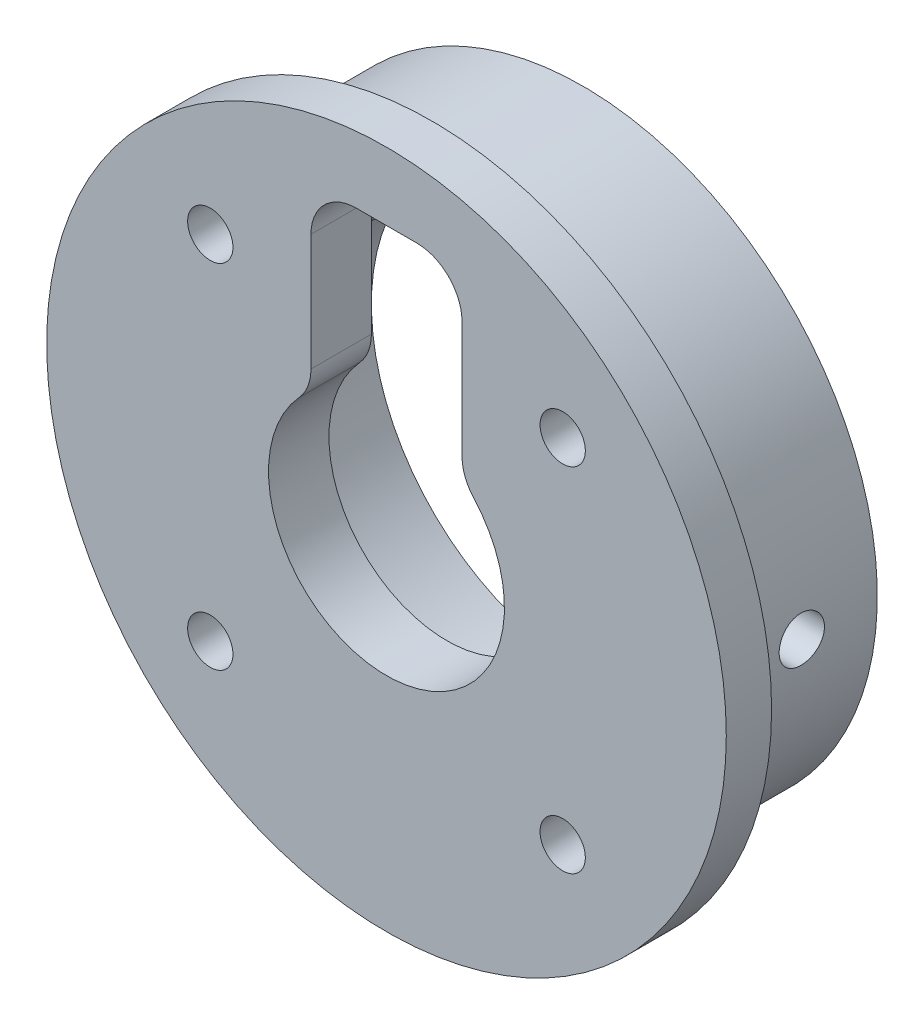
SolidWorks part; units mm, degrees
ref_plane "Front Plane" through (0, 0, 0) normal (0, 0, 1) x (1, 0, 0)
ref_plane "Top Plane" through (0, 0, 0) normal (0, 1, 0) x (1, 0, 0)
ref_plane "Right Plane" through (0, 0, 0) normal (1, 0, 0) x (0, 0, -1)
sketch "Sketch1" plane through (0, 0, 0) normal (0, 0, 1) x (1, 0, 0)
  circle A2 centre (750, 29.3136) radius 22.5
extrude "Boss-Extrude1" add sketch "Sketch1" along normal blind 3
sketch "Sketch2" plane through (0, 0, 0) normal (0, 0, -1) x (-1, 0, 0)
  circle A2 centre (-750, 29.3136) radius 19.5
  circle A3 centre (-750, 29.3136) radius 19.5
  dimension "D1" = 3
extrude "Boss-Extrude2" add sketch "Sketch2" along normal blind 10
sketch "Sketch3" plane through (0, 0, 3) normal (0, 0, 1) x (1, 0, 0)
  line L0 (750, 6.8136) -> (750, 29.3136) construction
  line L1 (750, 29.3136) -> (772.5, 29.3136) construction
  line L2 (750, 29.3136) -> (761.6673, 17.6464) construction
  line L4 (748, 47.3136) -> (752, 47.3136)
  line L5 (745, 44.3136) -> (745, 35.3136)
  line L7 (755, 44.3136) -> (755, 35.3136)
  circle A0 centre (750, 29.3136) radius 16.5 construction
  circle A1 centre (750, 29.3136) radius 22.5 construction
  circle A2 centre (761.6673, 17.6464) radius 1.5
  circle A3 centre (738.3327, 17.6464) radius 1.5
  circle A4 centre (738.3327, 40.9809) radius 1.5
  circle A5 centre (761.6673, 40.9809) radius 1.5
  arc A6 (745, 35.3136) -> (755, 35.3136) centre (750, 29.3136) ccw
  arc A7 (752, 47.3136) -> (755, 44.3136) centre (752, 44.3136) cw
  arc A8 (748, 47.3136) -> (745, 44.3136) centre (748, 44.3136) ccw
  point P18 (750, 29.3136)
  point P22 (755, 47.3136)
  point P25 (745, 47.3136)
  dimension "D1" = 4
extrude "Cut-Extrude1" cut sketch "Sketch3" against normal up to surface (13 mm away) up to face at (730.5, 29.3136, -10)
sketch "Sketch4" plane through (745, 0, 0) normal (1, 0, 0) x (0, 0, -1)
  circle A0 centre (5, 29.3136) radius 1.5
extrude "Cut-Extrude2" cut sketch "Sketch4" against normal through all both and the other way through all
sketch "Sketch5" plane through (0, 0, -10) normal (0, 0, -1) x (-1, 0, 0)
  circle A0 centre (-750, 29.3136) radius 14
extrude "Cut-Extrude3" cut sketch "Sketch5" against normal blind 9
fillet "Fillet1" radius 3 4 edges at (755, 35.3136, 1) (745, 35.3136, 1) (755, 42.3903, -5.5) (745, 42.3903, -5.5)
